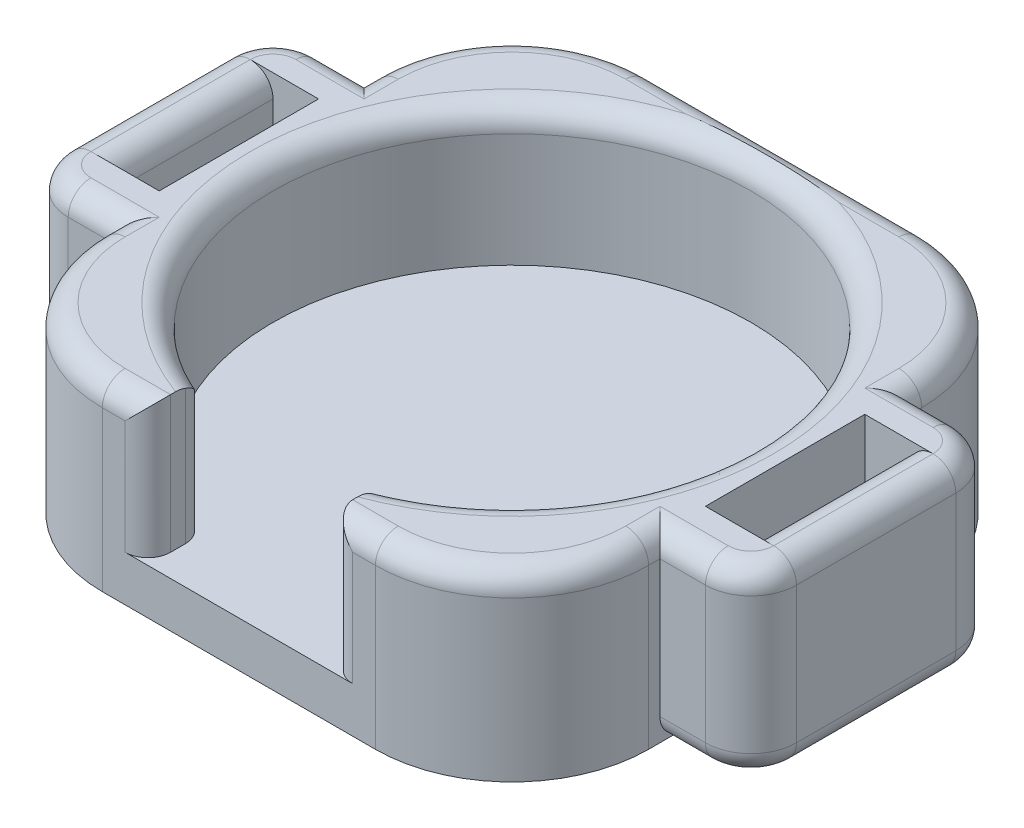
SolidWorks part; units mm, degrees
ref_plane "Front Plane" through (0, 0, 0) normal (0, 0, 1) x (1, 0, 0)
ref_plane "Top Plane" through (0, 0, 0) normal (0, 1, 0) x (1, 0, 0)
ref_plane "Right Plane" through (0, 0, 0) normal (1, 0, 0) x (0, 0, -1)
sketch "Sketch1" plane through (0, 0, 0) normal (0, 1, 0) x (1, 0, 0)
  line L1 (-112.5943, -49.3182) -> (-100.5943, -49.3182)
  line L2 (-112.5943, -49.3182) -> (-112.5943, -61.3182)
  line L3 (-112.5943, -61.3182) -> (-100.5943, -61.3182)
  line L4 (-100.5943, -49.3182) -> (-100.5943, -61.3182)
extrude "Boss-Extrude2" add sketch "Sketch1" along normal blind 4
sketch "Sketch3" plane through (0, 4, 0) normal (0, 1, 0) x (1, 0, 0)
  circle A0 centre (-106.5943, -55.3182) radius 5.25
extrude "Cut-Extrude1" cut sketch "Sketch3" against normal blind 3
sketch "Sketch4" plane through (0, 4, 0) normal (0, 1, 0) x (1, 0, 0)
  line L0 (-100.5943, -55.3182) -> (-100.5943, -52.5682)
  line L1 (-100.5943, -61.3182) -> (-100.5943, -49.3182) construction
  line L2 (-100.5943, -55.3182) -> (-100.5943, -58.0682)
  line L3 (-112.5943, -58.0682) -> (-112.5943, -52.5682)
  line L4 (-112.5943, -49.3182) -> (-112.5943, -61.3182) construction
  line L5 (-112.5943, -55.3182) -> (-111.8443, -55.3182)
  line L6 (-112.5943, -52.5682) -> (-114.5943, -52.5682)
  line L7 (-112.5943, -58.0682) -> (-114.5943, -58.0682)
  line L8 (-114.5943, -58.0682) -> (-114.5943, -52.5682)
  line L9 (-100.5943, -52.5682) -> (-98.5943, -52.5682)
  line L10 (-98.5943, -52.5682) -> (-98.5943, -58.0682)
  line L11 (-98.5943, -58.0682) -> (-100.5943, -58.0682)
  line M5 (-112.5943, -49.3182) -> (-112.5943, -61.3182)
  line M7 (-100.5943, -61.3182) -> (-100.5943, -49.3182)
extrude "Boss-Extrude4" add sketch "Sketch4" against normal blind 4 contours L8 L7 L3 L6 M5 | L11 L10 L9 M7 region at (-99.5943, 4, 55.3182) region at (-113.5943, 4, 55.3182)
sketch "Sketch6" plane through (0, 4, 0) normal (0, 1, 0) x (1, 0, 0)
  line L0 (-114.5943, -55.3182) -> (-113.5943, -55.3182)
  line L1 (-114.5943, -58.0682) -> (-114.5943, -52.5682) construction
  line L2 (-113.5943, -55.3182) -> (-113.5943, -57.0682)
  line L3 (-113.5943, -55.3182) -> (-113.5943, -53.5682)
  line L4 (-113.5943, -53.5682) -> (-112.5943, -53.5682)
  line L5 (-112.5943, -53.5682) -> (-112.5943, -57.0682)
  line L6 (-112.5943, -57.0682) -> (-113.5943, -57.0682)
  line L7 (-98.5943, -55.3182) -> (-99.5943, -55.3182)
  line L8 (-98.5943, -52.5682) -> (-98.5943, -58.0682) construction
  line L9 (-99.5943, -55.3182) -> (-99.5943, -53.5682)
  line L10 (-99.5943, -53.5682) -> (-100.5943, -53.5682)
  line L11 (-99.5943, -55.3182) -> (-99.5943, -57.0682)
  line L12 (-99.5943, -57.0682) -> (-100.5943, -57.0682)
  line L13 (-100.5943, -57.0682) -> (-100.5943, -53.5682)
extrude "Cut-Extrude5" cut sketch "Sketch6" against normal blind 4 contours L6 L5 L4 L3 L2 | L13 L12 L11 L9 L10 region at (-113.0943, 4, 55.3182) region at (-100.0943, 4, 55.3182)
fillet "Fillet1" radius 1 4 edges at (-114.5943, 2, 52.5682) (-98.5943, 2, 52.5682) (-98.5943, 2, 58.0682) (-114.5943, 2, 58.0682)
fillet "Fillet2" radius 3 4 edges at (-112.5943, 2, 49.3182) (-100.5943, 2, 49.3182) (-100.5943, 2, 61.3182) (-112.5943, 2, 61.3182)
fillet "Fillet3" radius 0.5 24 edges at (-113.0943, 0, 58.0682) (-114.3014, 0, 57.7753) (-113.0943, 0, 52.5682) (-114.3014, 0, 52.8611) (-113.0943, 4, 58.0682) (-114.3014, 4, 57.7753) (-113.0943, 4, 52.5682) (-114.3014, 4, 52.8611) (-100.0943, 0, 52.5682) (-98.8872, 0, 52.8611) (-100.0943, 0, 58.0682) (-98.8872, 0, 57.7753) (-100.0943, 4, 52.5682) (-98.8872, 4, 52.8611) (-100.0943, 4, 58.0682) (-98.8872, 4, 57.7753) (-114.5943, 0, 55.3182) (-113.5943, 0, 55.3182) (-113.5943, 4, 55.3182) (-114.5943, 4, 55.3182) (-98.5943, 0, 55.3182) (-99.5943, 0, 55.3182) (-98.5943, 4, 55.3182) (-99.5943, 4, 55.3182)
sketch "Sketch7" plane through (0, 4, 0) normal (0, 1, 0) x (1, 0, 0)
  line L0 (-106.5943, -61.3182) -> (-108.5943, -61.3182)
  line L1 (-109.5943, -61.3182) -> (-103.5943, -61.3182) construction
  line L2 (-106.5943, -61.3182) -> (-104.5943, -61.3182)
  line L3 (-104.5943, -60.1723) -> (-104.5943, -61.3182)
  line L4 (-108.5943, -60.1723) -> (-108.5943, -61.3182)
  line L5 (-104.5943, -61.3182) -> (-108.5943, -61.3182)
  circle A0 centre (-106.5943, -55.3182) radius 5.25
  circle M4 centre (-106.5943, -55.3182) radius 5.25
  line M15 (-109.5943, -61.3182) -> (-103.5943, -61.3182)
extrude "Cut-Extrude6" cut sketch "Sketch7" against normal blind 3 contours L4 L3 M4 M15 region at (-106.5943, 4, 60.8704)
fillet "Fillet4" radius 0.5 16 edges at (-106.5943, 4, 50.0682) (-104.5943, 2.5, 61.3182) (-104.5943, 2.5, 60.1723) (-108.5943, 2.5, 60.1723) (-108.5943, 2.5, 61.3182) (-100.5943, 4, 52.6932) (-112.5943, 4, 52.6932) (-111.7156, 4, 50.1969) (-106.5943, 4, 49.3182) (-104.0943, 4, 61.3182) (-100.5943, 4, 57.9432) (-112.5943, 4, 57.9432) (-111.7156, 4, 60.4395) (-101.4729, 4, 50.1969) (-101.4729, 4, 60.4395) (-109.0943, 4, 61.3182)
